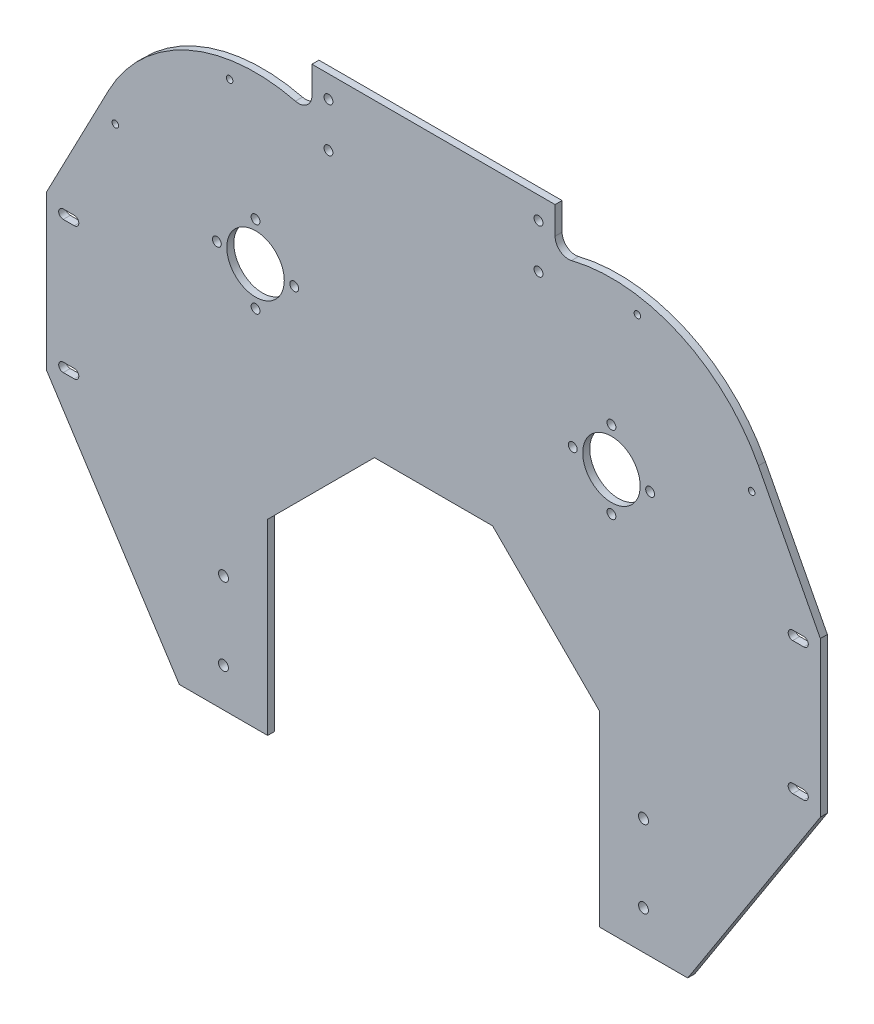
SolidWorks part; units mm, degrees
ref_plane "Front Plane" through (0, 0, 0) normal (0, 0, 1) x (1, 0, 0)
ref_plane "Top Plane" through (0, 0, 0) normal (0, 1, 0) x (1, 0, 0)
ref_plane "Right Plane" through (0, 0, 0) normal (1, 0, 0) x (0, 0, -1)
sketch "Sketch1" plane through (0, 0, 0) normal (0, 0, 1) x (1, 0, 0)
  line L1 (-100, -75) -> (100, -75)
  line L2 (-100, -75) -> (-100, 75)
  line L3 (-100, 75) -> (100, 75)
  line L4 (100, -75) -> (100, 75)
  line L5 (-100, -75) -> (100, 75) construction
  line L6 (-100, 75) -> (100, -75) construction
  line L8 (-47.5, 40) -> (47.5, 40) construction
  line L9 (0, 75) -> (0, -75) construction
  line L10 (-27, -44) -> (27, -44) construction
  line L11 (-27, -44) -> (-27, 28) construction
  line L12 (-27, 28) -> (27, 28) construction
  line L13 (27, -44) -> (27, 28) construction
  line L14 (-27, -44) -> (27, 28) construction
  line L15 (-27, 28) -> (27, -44) construction
  line L23 (-55, 70) -> (55, 70)
  line L24 (-55, 70) -> (-55, -70)
  line L25 (-55, -70) -> (55, -70)
  line L26 (55, 70) -> (55, -70)
  line L27 (-55, 70) -> (55, -70) construction
  line L28 (-55, -70) -> (55, 70) construction
  line L29 (-32.5, 70) -> (32.5, 70) construction
  line L30 (-32.5, 70) -> (-32.5, 55) construction
  line L31 (-32.5, 55) -> (32.5, 55) construction
  line L32 (32.5, 70) -> (32.5, 55) construction
  line L33 (-32.5, 70) -> (32.5, 55) construction
  line L34 (-32.5, 55) -> (32.5, 70) construction
  circle A2 centre (-47.5, 40) radius 2
  circle A3 centre (47.5, 40) radius 2
  circle A4 centre (-27, 28) radius 2 construction
  circle A5 centre (27, 28) radius 2 construction
  circle A6 centre (27, -44) radius 2 construction
  circle A7 centre (-27, -44) radius 2 construction
  circle A8 centre (-47.5, 60) radius 2
  circle A10 centre (47.5, 60) radius 2
  point P0 (0, 0)
  point P15 (0, 40)
  point P18 (0, -8)
  point P56 (0, 0)
  point P63 (0, 62.5)
  dimension "D3" = 4
  dimension "D4" = 20
  dimension "D5" = 4
  dimension "D8" = 4
  dimension "D1" = 150
  dimension "D2" = 200
  dimension "D6" = 72
  dimension "D7" = 54
  dimension "D14" = 30
  dimension "D15" = 140
  dimension "D16" = 110
  dimension "D17" = 95
  dimension "D18" = 12
  dimension "D19" = 15
  dimension "D20" = 65
extrude "Boss-Extrude1" add sketch "Sketch1" along normal blind 3.175 contours L23 L32 L31 L30 L24 L25 L26 A7 A6 A5 A4 A3 A2 region at (0, -0.1637, 0)
sketch "Sketch2" plane through (0, 0, 0) normal (0, 0, 1) x (1, 0, 0)
  line L0 (-55, -70) -> (-100.8579, -115.8579) construction
  line L1 (-55, 70) -> (-55, -70) construction
  line L2 (-55, -41.7157) -> (-115, -101.7157)
  line L3 (-26.7157, -70) -> (-86.7157, -130)
  line L4 (-55, -70) -> (55, -70) construction
  line L5 (-115, -101.7157) -> (-86.7157, -130)
  line L6 (-115, -101.7157) -> (-115, -203)
  line L7 (-75, -118.2843) -> (-75, -203)
  line L8 (-75, -203) -> (-115, -203)
  line L9 (0, 75) -> (0, -75) construction
  line L10 (-55, -41.7157) -> (-26.7157, -70)
  line L11 (-55, 70) -> (-55, -70) construction
  line L12 (-115, -203) -> (-66.3325, -203) construction
  circle A0 centre (-95, -150.5) radius 2.25
  circle A1 centre (-95, -185.5) radius 2.25
  circle A2 centre (-95, -150.5) radius 2.25 construction
  circle A4 centre (-95, -185.5) radius 2.25 construction
  dimension "D1" = 135
  dimension "D2" = 40
  dimension "D3" = 40
  dimension "D4" = 75
  dimension "D5" = 0
extrude "Boss-Extrude2" add sketch "Sketch2" along normal blind 3.175 contours L8 L7 L3 L5 L6 | L10 L2 L5 L3 region at (-70.8579, -85.8579, 0) region at (-95.9307, -160.1869, 0)
mirror "Mirror1" about plane through (0, 0, 0) normal (1, 0, 0) of "Boss-Extrude2"
sketch "Sketch3" plane through (0, 0, 3.175) normal (0, 0, 1) x (1, 0, 0)
  line L0 (0, 31.3301) -> (0, 52.1198) construction
  line L1 (-80.5, -21) -> (-92.2213, 45.4745) construction
  line L2 (-80.5, -21) -> (80.5, -21) construction
  line L3 (-80.5, -21) -> (-148, -21) construction
  line L4 (-80.5, -21) -> (-143.9293, 2.0864) construction
  circle A0 centre (-80.5, -21) radius 75
  circle A1 centre (-80.5, -3.5) radius 2
  circle A2 centre (80.5, -21) radius 75
  circle A3 centre (-80.5, -21) radius 60
  circle A4 centre (80.5, -21) radius 60
  circle A5 centre (-47.5, 40) radius 2 construction
  circle A6 centre (-47.5, 40) radius 2
  circle A7 centre (47.5, 40) radius 2
  circle A8 centre (-63, -21) radius 2
  circle A9 centre (-80.5, -38.5) radius 2
  circle A10 centre (-98, -21) radius 2
  circle A11 centre (98, -21) radius 2
  circle A12 centre (80.5, -38.5) radius 2
  circle A13 centre (63, -21) radius 2
  circle A14 centre (80.5, -3.5) radius 2
  circle A15 centre (-80.5, -21) radius 13
  circle A16 centre (80.5, -21) radius 13
  circle A17 centre (-92.2213, 45.4745) radius 1.4732
  circle A18 centre (-143.9293, 2.0864) radius 1.4732
  circle A19 centre (-80.5, -21) radius 67.5 construction
  circle A20 centre (92.2213, 45.4745) radius 1.4732
  circle A21 centre (143.9293, 2.0864) radius 1.4732
  point P28 (-80.5, -21)
  line M3 (115, -101.7157) -> (55, -41.7157)
  line M4 (55, -41.7157) -> (55, 70)
  line M6 (-55, 70) -> (-55, -41.7157)
  line M7 (-55, -41.7157) -> (-115, -101.7157)
  line M11 (-75, -118.2843) -> (-26.7157, -70)
  line M12 (-26.7157, -70) -> (26.7157, -70)
  line M13 (26.7157, -70) -> (75, -118.2843)
  circle M17 centre (-47.5, 40) radius 2
  circle M18 centre (47.5, 40) radius 2
  dimension "D1" = 161
  dimension "D2" = 150
  dimension "D3" = 61
  dimension "D4" = 120
  dimension "D5" = 4
  dimension "D7" = 35
  dimension "D8" = 26
  dimension "D9" = 7.5
  dimension "D10" = 2.9464
  dimension "D6" = 4
  dimension "D11" = 80
  dimension "D12" = 20
extrude "Boss-Extrude3" add sketch "Sketch3" against normal up to surface (3.175 mm away) contours A3 M6 M7 | A3 A0 M6 M7 | A3 A0 M7 M11 M12 M6 M17 | A3 M7 M6 | A4 M3 M4 | A4 M4 M3 | A4 A2 M4 M3 | A4 A2 M3 M4 M12 M13 M18 region at (-11.8554, -46.5242, 3.175) region at (9.6495, -2.4591, 3.175) region at (-56.7712, 41.4218, 3.175) region at (-96.2806, -16.4848, 3.175) region at (-46.5969, -30.7004, 3.175) region at (122.5668, 38.9404, 3.175) region at (46.5969, -30.7004, 3.175) region at (96.2806, -16.4848, 3.175) up to face at (0, -95.388, 0)
sketch "Sketch4" plane through (0, 0, 3.175) normal (0, 0, 1) x (1, 0, 0)
  line L0 (-175, -75) -> (-100, -75) construction
  line L1 (-100, -40) -> (-153.0534, -40)
  line L2 (-100, -40) -> (-100, -110)
  line L3 (-100, -110) -> (-115, -110) construction
  line L4 (-175, -40) -> (-175, -110)
  line L5 (-100, -40) -> (-175, -110) construction
  line L6 (-100, -110) -> (-175, -40) construction
  line L7 (-175, -110) -> (-115, -203)
  line L9 (-115, -101.7157) -> (-115, -203) construction
  line L10 (-115, -110) -> (-115, -203)
  line L11 (-175, -40) -> (-146.9976, 13.6853)
  line L12 (-153.0534, -40) -> (-175, -40)
  line L13 (-100, -110) -> (-115, -110) construction
  line L14 (-100, -110) -> (-100, -101.7157)
  line L15 (-100, -101.7157) -> (-115, -101.7157)
  line L16 (-115, -110) -> (-115, -101.7157)
  line L17 (-100, -110) -> (-115, -101.7157) construction
  line L18 (-100, -101.7157) -> (-115, -110) construction
  line L19 (-151.1989, -110) -> (-175, -110) construction
  line L21 (-165, -75) -> (-165, -40) construction
  line L22 (-162.5, -45) -> (-167.5, -45) construction
  line L23 (-162.5, -47.05) -> (-167.5, -47.05)
  line L24 (-162.5, -42.95) -> (-167.5, -42.95)
  line L25 (-162.5, -105) -> (-167.5, -105) construction
  line L26 (-162.5, -102.95) -> (-167.5, -102.95)
  line L27 (-162.5, -107.05) -> (-167.5, -107.05)
  arc A0 (-55, 49.5319) -> (-105.1261, -91.8418) centre (-80.5, -21) ccw construction
  arc A1 (-146.9976, 13.6853) -> (-153.0534, -40) centre (-80.5, -21) ccw
  circle A2 centre (-165, -45) radius 2.05 construction
  arc A3 (-162.5, -47.05) -> (-162.5, -42.95) centre (-162.5, -45) ccw
  arc A4 (-167.5, -42.95) -> (-167.5, -47.05) centre (-167.5, -45) ccw
  arc A5 (-162.5, -102.95) -> (-162.5, -107.05) centre (-162.5, -105) cw
  arc A6 (-167.5, -107.05) -> (-167.5, -102.95) centre (-167.5, -105) cw
  point P4 (-137.5, -75)
  point P23 (-107.5, -105.8579)
  point P32 (-165, -45)
  point P40 (-165, -105)
  arc M12 (-55, 49.5319) -> (-105.1261, -91.8418) centre (-80.5, -21) ccw
  line M13 (-105.1261, -91.8418) -> (-115, -101.7157)
  line M14 (-115, -101.7157) -> (-115, -203)
  circle M41 centre (-143.9293, 2.0864) radius 1.4732
  dimension "D7" = 4.1
  dimension "D8" = 2.05
  dimension "D1" = 40
  dimension "D2" = 100
  dimension "D3" = 70
  dimension "D4" = 75
  dimension "D6" = 10
  dimension "D9" = 5
  dimension "D10" = 5
extrude "Boss-Extrude5" add sketch "Sketch4" against normal up to surface (3.175 mm away) contours L16 L12 L4 L7 A4 L24 A3 L23 L27 A6 L26 A5 M13 M12 M14 | L15 L14 L2 L1 M12 M13 M41 | L12 L11 M12 region at (-120.1023, -62.6792, 3.175) region at (-142.6858, -110.2719, 3.175) region at (-161.1873, -26.2241, 3.175) up to face at (0, -80.3864, 0)
mirror "Mirror2" about plane through (0, 0, 0) normal (1, 0, 0) of "Boss-Extrude5"
fillet "Fillet1" radius 6 2 edges at (55, 49.5319, 1.5875) (-55, 49.5319, 1.5875)
